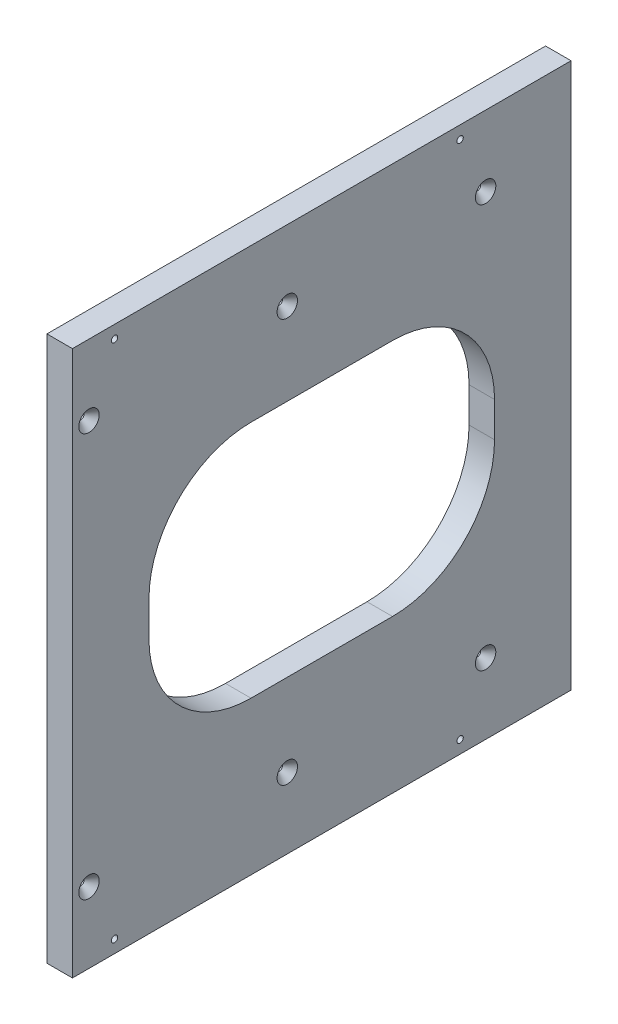
SolidWorks part; units mm, degrees
material "Beech"
ref_plane "Front Plane" through (0, 0, 0) normal (0, 0, 1) x (1, 0, 0)
ref_plane "Top Plane" through (0, 0, 0) normal (0, 1, 0) x (1, 0, 0)
ref_plane "Right Plane" through (0, 0, 0) normal (1, 0, 0) x (0, 0, -1)
sketch "Sketch1" plane through (0, 0, 0) normal (0, 0, 1) x (1, 0, 0)
  line L0 (-234.753, -188.5238) -> (-91.9973, -188.5238) construction
  line L1 (-234.753, 82.8417) -> (-222.053, 82.8417)
  line L2 (-234.753, 82.8417) -> (-234.753, -188.5238)
  line L3 (-234.753, -188.5238) -> (-222.053, -188.5238)
  line L4 (-222.053, 82.8417) -> (-222.053, -188.5238)
  dimension "D1" = 12.7
extrude "Boss-Extrude1" add sketch "Sketch1" along normal offset from surface (248.25 mm away) 19.05
sketch "Sketch2" plane through (-234.753, 0, 0) normal (-1, 0, 0) x (0, 0, 1)
  line L0 (124.125, 82.8417) -> (124.125, -52.841) construction
  line L1 (248.25, 82.8417) -> (0, 82.8417) construction
  line L2 (124.125, -52.841) -> (248.25, -52.841) construction
  line L3 (248.25, 82.8417) -> (248.25, -188.5238) construction
  line L5 (38.1, -112.3238) -> (210.15, -112.3238)
  line L6 (38.1, -112.3238) -> (38.1, 6.6417)
  line L7 (38.1, 6.6417) -> (210.15, 6.6417)
  line L8 (210.15, -112.3238) -> (210.15, 6.6417)
  line L9 (38.1, -112.3238) -> (210.15, 6.6417) construction
  line L10 (38.1, 6.6417) -> (210.15, -112.3238) construction
  dimension "D1" = 38.1
  dimension "D2" = 76.2
extrude "Cut-Extrude1" cut sketch "Sketch2" against normal through all
fillet "Fillet1" radius 50.8 4 edges at (-228.403, 6.6417, 38.1) (-228.403, -112.3238, 38.1) (-228.403, -112.3238, 210.15) (-228.403, 6.6417, 210.15)
hole_wizard "Hole1" positions "Sketch3" profile "Sketch4" legacy
sketch "Sketch3" plane through (181.0394, -52.975, -12.7) normal (0, 0, -1) x (0, -1, 0)
  line L0 (-129.4667, 415.7924) -> (-129.4667, 273.0368) construction
  line L5 (-135.8167, 409.4424) -> (135.5488, 409.4424) construction
  line L10 (-135.8167, 279.3868) -> (135.5488, 279.3868) construction
  line L11 (-0.134, 409.4424) -> (-0.134, 279.3868) construction
  point P22 (-129.4667, 384.0424)
  point P24 (-129.4667, 304.7868)
  point P26 (-110.4167, 409.4424)
  point P30 (-0.134, 409.4424)
  point P50 (110.1488, 409.4424)
  point P51 (129.1988, 304.7868)
  point P52 (129.1988, 384.0424)
sketch "Sketch4" plane through (-203.003, -182.1738, -12.7) normal (1, 0, 0) x (0, 1, 0)
  line L0 (0, 0) -> (0, 32.7039)
  line L1 (0, 32.7039) -> (1.5875, 31.75)
  line L2 (1.5875, 31.75) -> (1.5875, 4.0177)
  line L3 (1.5875, 4.0177) -> (5.08, 0)
  line L4 (5.08, 0) -> (0, 0)
  line L5 (0, -14.3089) -> (0, 102.4216) construction
  line L6 (0, 32.7039) -> (-1.5875, 31.75) construction
  line L7 (-1.5875, 4.0177) -> (-5.08, 0) construction
  dimension "Diameter" = 3.175
  dimension "Depth" = 31.75
  dimension "C-Sink Diameter" = 10.16
  dimension "C-Sink Angle" = 82
  dimension "Drill Angle" = 118
hole_wizard "Hole2" positions "Sketch5" profile "Sketch6" legacy
sketch "Sketch5" plane through (-234.753, -52.975, -1073.3642) normal (-1, 0, 0) x (0, -1, 0)
  line L3 (-0.134, 1338.7628) -> (-0.134, 1090.5128) construction
  point P1 (-129.4667, 1300.6628)
  point P3 (-129.4667, 1128.6128)
  point P15 (129.1988, 1128.6128)
  point P16 (129.1988, 1300.6628)
sketch "Sketch6" plane through (-234.753, 76.4917, 227.2986) normal (0, 1, 0) x (0, 0, 1)
  line L0 (0, 0) -> (0, 32.7039)
  line L1 (0, 32.7039) -> (1.5875, 31.75)
  line L2 (1.5875, 31.75) -> (1.5875, 4.0177)
  line L3 (1.5875, 4.0177) -> (5.08, 0)
  line L4 (5.08, 0) -> (0, 0)
  line L5 (0, -14.3089) -> (0, 102.4216) construction
  line L6 (0, 32.7039) -> (-1.5875, 31.75) construction
  line L7 (-1.5875, 4.0177) -> (-5.08, 0) construction
  dimension "Diameter" = 3.175
  dimension "Depth" = 31.75
  dimension "C-Sink Diameter" = 10.16
  dimension "C-Sink Angle" = 82
  dimension "Drill Angle" = 118
hole_wizard "Hole3" positions "Sketch7" profile "Sketch8" legacy
sketch "Sketch7" plane through (-222.053, -52.975, -1073.3642) normal (1, 0, 0) x (0, 1, 0)
  line L0 (100.6, 1338.7628) -> (100.6, 1090.5128) construction
  line L6 (0.134, 1338.7628) -> (0.134, 1090.5128) construction
  point P12 (100.6, 1313.3628)
  point P14 (100.6, 1115.9128)
  point P16 (100.6, 1214.6378)
  point P22 (-100.332, 1214.6378)
  point P23 (-100.332, 1115.9128)
  point P24 (-100.332, 1313.3628)
sketch "Sketch8" plane through (-222.053, -153.307, 239.9986) normal (0, 1, 0) x (0, 0, -1)
  line L0 (0, 0) -> (0, 32.7039)
  line L1 (0, 32.7039) -> (1.5875, 31.75)
  line L2 (1.5875, 31.75) -> (1.5875, 4.0177)
  line L3 (1.5875, 4.0177) -> (5.08, 0)
  line L4 (5.08, 0) -> (0, 0)
  line L5 (0, -14.3089) -> (0, 102.4216) construction
  line L6 (0, 32.7039) -> (-1.5875, 31.75) construction
  line L7 (-1.5875, 4.0177) -> (-5.08, 0) construction
  dimension "Diameter" = 3.175
  dimension "Depth" = 31.75
  dimension "C-Sink Diameter" = 10.16
  dimension "C-Sink Angle" = 82
  dimension "Drill Angle" = 118
